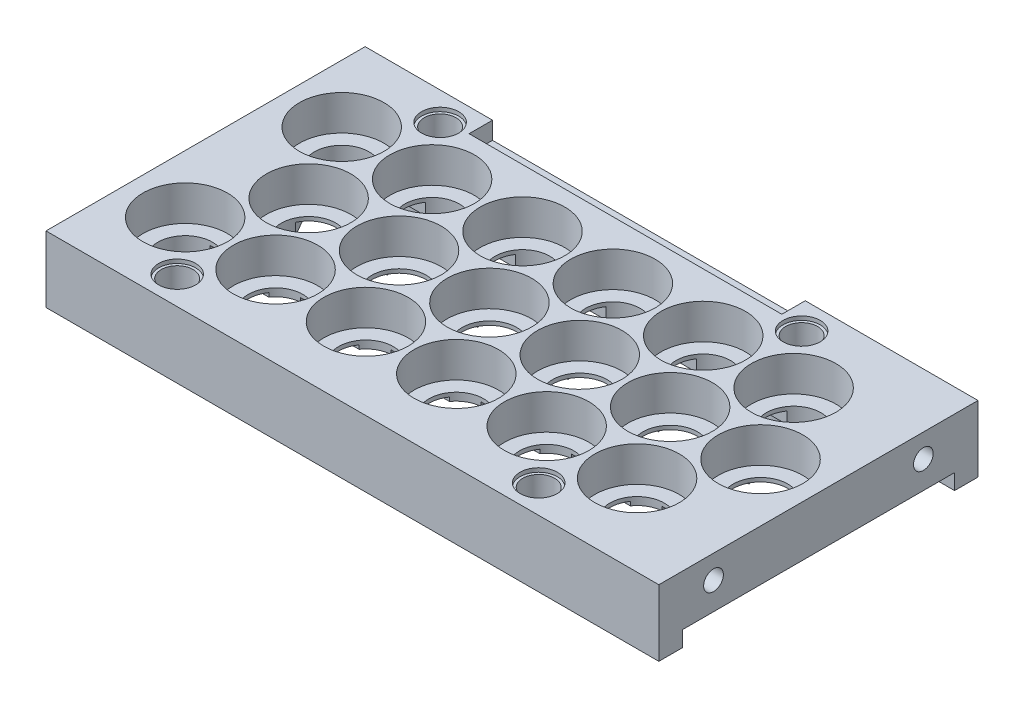
SolidWorks part; units mm, degrees
ref_plane "Front Plane" through (0, 0, 0) normal (0, 0, 1) x (1, 0, 0)
ref_plane "Top Plane" through (0, 0, 0) normal (0, 1, 0) x (1, 0, 0)
ref_plane "Right Plane" through (0, 0, 0) normal (1, 0, 0) x (0, 0, -1)
sketch "Sketch1" plane through (0, 0, 0) normal (0, 1, 0) x (1, 0, 0)
  line L0 (0, 0) -> (11.575, -20.0485) construction
  line L1 (11.575, -20.0485) -> (0, -40.097) construction
  line L2 (0, 0) -> (11.575, 0) construction
  line L3 (11.575, 0) -> (11.575, -20.0485) construction
  line L4 (11.575, -20.0485) -> (11.575, -40.097) construction
  line L5 (11.575, -40.097) -> (0, -40.097) construction
  line L6 (0, 0) -> (23.15, 0) construction
  line L7 (0, 0) -> (23.15, 0) construction
  line L8 (-14.825, -60.922) -> (142.15, -60.922)
  line L9 (-14.825, -60.922) -> (-14.825, 20.825)
  line L10 (-14.825, 20.825) -> (142.15, 20.825)
  line L11 (142.15, -60.922) -> (142.15, 20.825)
  circle A0 centre (0, 0) radius 10.825
  circle A1 centre (11.575, -20.0485) radius 10.825
  circle A2 centre (0, -40.097) radius 10.825
  circle A3 centre (23.15, 0) radius 10.825
  circle A4 centre (34.725, -20.0485) radius 10.825
  circle A5 centre (23.15, -40.097) radius 10.825
  circle A6 centre (46.3, 0) radius 10.825
  circle A7 centre (57.875, -20.0485) radius 10.825
  circle A8 centre (46.3, -40.097) radius 10.825
  circle A9 centre (69.45, 0) radius 10.825
  circle A10 centre (81.025, -20.0485) radius 10.825
  circle A11 centre (69.45, -40.097) radius 10.825
  circle A12 centre (92.6, 0) radius 10.825
  circle A13 centre (104.175, -20.0485) radius 10.825
  circle A14 centre (92.6, -40.097) radius 10.825
  circle A15 centre (115.75, 0) radius 10.825
  circle A16 centre (127.325, -20.0485) radius 10.825
  circle A17 centre (115.75, -40.097) radius 10.825
  circle A18 centre (0, 0) radius 7
  circle A19 centre (11.575, -20.0485) radius 7
  circle A20 centre (0, -40.097) radius 7
  circle A21 centre (23.15, 0) radius 7
  circle A22 centre (34.725, -20.0485) radius 7
  circle A23 centre (23.15, -40.097) radius 7
  circle A24 centre (46.3, 0) radius 7
  circle A25 centre (57.875, -20.0485) radius 7
  circle A26 centre (46.3, -40.097) radius 7
  circle A27 centre (69.45, 0) radius 7
  circle A28 centre (81.025, -20.0485) radius 7
  circle A29 centre (69.45, -40.097) radius 7
  circle A30 centre (92.6, 0) radius 7
  circle A31 centre (104.175, -20.0485) radius 7
  circle A32 centre (92.6, -40.097) radius 7
  circle A33 centre (115.75, 0) radius 7
  circle A34 centre (127.325, -20.0485) radius 7
  circle A35 centre (115.75, -40.097) radius 7
  dimension "D3" = 21.65
  dimension "D11" = 14
  dimension "D1" = 60
  dimension "D2" = 60
  dimension "D4" = 1.5
  dimension "D6" = 23.15
  dimension "D7" = 4
  dimension "D8" = 4
  dimension "D9" = 10
  dimension "D10" = 10
  dimension "D13" = 23.15
  dimension "D5" = 6
  dimension "D12" = 6
extrude "Boss-Extrude2" add sketch "Sketch1" along normal blind 11 contours L8 L11 L10 L9 A17 A16 A15 A14 A13 A12 A11 A10 A9 A8 A7 A6 A5 A4 A3 A2 A1 A0 region at (-13.0551, 0, 20.0485)
extrude "Boss-Extrude3" add sketch "Sketch1<3>" along normal blind 2 contours A0 A18 | A3 A21 | A6 A24 | A9 A27 | A12 A30 | A15 A33 | A1 A19 | A4 A22 | A7 A25 | A10 A28 | A13 A31 | A16 A34 | A17 A35 | A14 A32 | A11 A29 | A8 A26 | A5 A23 | A2 A20 region at (-10.5188, 0, 0) region at (1.0562, 0, 20.0485) region at (-10.5188, 0, 40.097) region at (12.6312, 0, 0) region at (24.2062, 0, 20.0485) region at (12.6312, 0, 40.097) region at (35.7812, 0, 0) region at (47.3562, 0, 20.0485) region at (35.7812, 0, 40.097) region at (58.9312, 0, 0) region at (70.5062, 0, 20.0485) region at (58.9312, 0, 40.097) region at (82.0812, 0, 0) region at (93.6562, 0, 20.0485) region at (82.0812, 0, 40.097) region at (105.2312, 0, 0) region at (116.8062, 0, 20.0485) region at (105.2312, 0, 40.097)
sketch "Sketch1<3>" plane through (0, 0, 0) normal (0, 1, 0) x (1, 0, 0) same geometry as "Sketch1"
sketch "Sketch2" plane through (0, 0, 0) normal (0, -1, 0) x (1, 0, 0)
  line L0 (0, 40.097) -> (11.575, 20.0485) construction
  line L1 (3.4641, 42.097) -> (15.0391, 22.0485)
  line L2 (-3.4641, 38.097) -> (8.1109, 18.0485)
  line L3 (11.575, 20.0485) -> (0, 0) construction
  line L4 (15.0391, 18.0485) -> (3.4641, -2)
  line L5 (8.1109, 22.0485) -> (-3.4641, 2)
  line L6 (19.6859, 38.097) -> (31.2609, 18.0485)
  line L7 (26.6141, 42.097) -> (38.1891, 22.0485)
  line L8 (31.2609, 22.0485) -> (19.6859, 2)
  line L9 (38.1891, 18.0485) -> (26.6141, -2)
  line L10 (23.15, 40.097) -> (34.725, 20.0485) construction
  line L11 (34.725, 20.0485) -> (23.15, 0) construction
  line L12 (42.8359, 38.097) -> (54.4109, 18.0485)
  line L13 (49.7641, 42.097) -> (61.3391, 22.0485)
  line L14 (54.4109, 22.0485) -> (42.8359, 2)
  line L15 (61.3391, 18.0485) -> (49.7641, -2)
  line L16 (46.3, 40.097) -> (57.875, 20.0485) construction
  line L17 (57.875, 20.0485) -> (46.3, 0) construction
  line L18 (65.9859, 38.097) -> (77.5609, 18.0485)
  line L19 (72.9141, 42.097) -> (84.4891, 22.0485)
  line L20 (77.5609, 22.0485) -> (65.9859, 2)
  line L21 (84.4891, 18.0485) -> (72.9141, -2)
  line L22 (69.45, 40.097) -> (81.025, 20.0485) construction
  line L23 (81.025, 20.0485) -> (69.45, 0) construction
  line L24 (89.1359, 38.097) -> (100.7109, 18.0485)
  line L25 (96.0641, 42.097) -> (107.6391, 22.0485)
  line L26 (100.7109, 22.0485) -> (89.1359, 2)
  line L27 (107.6391, 18.0485) -> (96.0641, -2)
  line L28 (92.6, 40.097) -> (104.175, 20.0485) construction
  line L29 (104.175, 20.0485) -> (92.6, 0) construction
  line L30 (112.2859, 38.097) -> (123.8609, 18.0485)
  line L31 (119.2141, 42.097) -> (130.7891, 22.0485)
  line L32 (123.8609, 22.0485) -> (112.2859, 2)
  line L33 (130.7891, 18.0485) -> (119.2141, -2)
  line L34 (115.75, 40.097) -> (127.325, 20.0485) construction
  line L35 (127.325, 20.0485) -> (115.75, 0) construction
  line L36 (-3.4641, 38.097) -> (19.6859, 38.097) construction
  line L37 (0, 40.097) -> (115.75, 40.097) construction
  line L38 (0, 44.097) -> (115.75, 44.097)
  line L39 (0, 36.097) -> (115.75, 36.097)
  line L40 (11.575, 20.0485) -> (127.325, 20.0485) construction
  line L41 (11.575, 24.0485) -> (127.325, 24.0485)
  line L42 (11.575, 16.0485) -> (127.325, 16.0485)
  line L43 (0, 0) -> (115.75, 0) construction
  line L44 (0, 4) -> (115.75, 4)
  line L45 (0, -4) -> (115.75, -4)
  arc A0 (3.4641, 42.097) -> (-3.4641, 38.097) centre (0, 40.097) ccw
  arc A1 (8.1109, 18.0485) -> (15.0391, 22.0485) centre (11.575, 20.0485) ccw
  arc A2 (15.0391, 18.0485) -> (8.1109, 22.0485) centre (11.575, 20.0485) ccw
  arc A3 (-3.4641, 2) -> (3.4641, -2) centre (0, 0) ccw
  arc A4 (26.6141, 42.097) -> (19.6859, 38.097) centre (23.15, 40.097) ccw
  arc A5 (31.2609, 18.0485) -> (38.1891, 22.0485) centre (34.725, 20.0485) ccw
  arc A6 (38.1891, 18.0485) -> (31.2609, 22.0485) centre (34.725, 20.0485) ccw
  arc A7 (19.6859, 2) -> (26.6141, -2) centre (23.15, 0) ccw
  arc A8 (49.7641, 42.097) -> (42.8359, 38.097) centre (46.3, 40.097) ccw
  arc A9 (54.4109, 18.0485) -> (61.3391, 22.0485) centre (57.875, 20.0485) ccw
  arc A10 (61.3391, 18.0485) -> (54.4109, 22.0485) centre (57.875, 20.0485) ccw
  arc A11 (42.8359, 2) -> (49.7641, -2) centre (46.3, 0) ccw
  arc A12 (72.9141, 42.097) -> (65.9859, 38.097) centre (69.45, 40.097) ccw
  arc A13 (77.5609, 18.0485) -> (84.4891, 22.0485) centre (81.025, 20.0485) ccw
  arc A14 (84.4891, 18.0485) -> (77.5609, 22.0485) centre (81.025, 20.0485) ccw
  arc A15 (65.9859, 2) -> (72.9141, -2) centre (69.45, 0) ccw
  arc A16 (96.0641, 42.097) -> (89.1359, 38.097) centre (92.6, 40.097) ccw
  arc A17 (100.7109, 18.0485) -> (107.6391, 22.0485) centre (104.175, 20.0485) ccw
  arc A18 (107.6391, 18.0485) -> (100.7109, 22.0485) centre (104.175, 20.0485) ccw
  arc A19 (89.1359, 2) -> (96.0641, -2) centre (92.6, 0) ccw
  arc A20 (119.2141, 42.097) -> (112.2859, 38.097) centre (115.75, 40.097) ccw
  arc A21 (123.8609, 18.0485) -> (130.7891, 22.0485) centre (127.325, 20.0485) ccw
  arc A22 (130.7891, 18.0485) -> (123.8609, 22.0485) centre (127.325, 20.0485) ccw
  arc A23 (112.2859, 2) -> (119.2141, -2) centre (115.75, 0) ccw
  arc A24 (0, 44.097) -> (0, 36.097) centre (0, 40.097) ccw
  arc A25 (115.75, 36.097) -> (115.75, 44.097) centre (115.75, 40.097) ccw
  arc A26 (11.575, 24.0485) -> (11.575, 16.0485) centre (11.575, 20.0485) ccw
  arc A27 (127.325, 16.0485) -> (127.325, 24.0485) centre (127.325, 20.0485) ccw
  arc A28 (0, 4) -> (0, -4) centre (0, 0) ccw
  arc A29 (115.75, -4) -> (115.75, 4) centre (115.75, 0) ccw
  point P3 (5.7875, 30.0727)
  point P8 (5.7875, 10.0242)
  point P18 (28.9375, 30.0727)
  point P25 (28.9375, 10.0242)
  point P34 (52.0875, 30.0727)
  point P39 (52.0875, 10.0242)
  point P48 (75.2375, 30.0727)
  point P53 (75.2375, 10.0242)
  point P62 (98.3875, 30.0727)
  point P67 (98.3875, 10.0242)
  point P76 (121.5375, 30.0727)
  point P81 (121.5375, 10.0242)
  point P91 (57.875, 40.097)
  point P96 (69.45, 20.0485)
  point P103 (57.875, 0)
  circle M62 centre (0, 0) radius 7
  circle M63 centre (23.15, 0) radius 7
  circle M64 centre (46.3, 0) radius 7
  circle M65 centre (69.45, 0) radius 7
  circle M66 centre (92.6, 0) radius 7
  circle M67 centre (115.75, 0) radius 7
  circle M68 centre (11.575, 20.0485) radius 7
  circle M69 centre (34.725, 20.0485) radius 7
  circle M70 centre (57.875, 20.0485) radius 7
  circle M71 centre (81.025, 20.0485) radius 7
  circle M72 centre (104.175, 20.0485) radius 7
  circle M73 centre (127.325, 20.0485) radius 7
  circle M74 centre (115.75, 40.097) radius 7
  circle M75 centre (92.6, 40.097) radius 7
  circle M76 centre (69.45, 40.097) radius 7
  circle M77 centre (46.3, 40.097) radius 7
  circle M78 centre (23.15, 40.097) radius 7
  circle M79 centre (0, 40.097) radius 7
  dimension "D1" = 8
  dimension "D3" = 23.15
  dimension "D4" = 8
  dimension "D5" = 8
  dimension "D6" = 8
extrude "Cut-Extrude1" cut sketch "Sketch2" against normal blind 1 contours L1 L39 L38 M78 M79 | L7 L39 L38 M77 M78 | L39 L2 L1 M79 M68 | L42 L8 L6 L41 M68 M69 | L6 L41 L7 L39 M69 M78 | L12 L41 L13 L39 M70 M77 | L13 L39 L38 M76 M77 | L18 L41 L19 L39 M71 M76 | L19 L39 L38 M75 M76 | L24 L41 L25 L39 M72 M75 | L25 L39 L38 M74 M75 | L30 L41 L31 M73 M74 | L42 L32 L30 L41 M72 M73 | L42 L26 L24 L41 M71 M72 | L42 L20 L18 L41 M70 M71 | L42 L14 L12 L41 M69 M70 | L45 L44 L4 M62 M63 | L44 L4 L5 M62 M68 | L45 L44 L9 M63 M64 | L45 L44 L15 M64 M65 | L45 L44 L21 M65 M66 | L45 L44 L27 M66 M67 | L44 L27 L42 L26 M66 M72 | L42 L32 L33 M67 M73 | L44 L21 L42 L20 M65 M71 | L44 L15 L42 L14 M64 M70 | L39 L13 M77 | L39 L25 M75 | L39 L19 M76 | L41 L6 M69 | L44 L4 M62 | L44 L15 M64 | L44 L21 M65 | L44 L27 M66 | L41 L30 M73 | L32 L42 M73 | L41 L24 M72 | L26 L42 M72 | L41 L18 M71 | L20 L42 M71 | L41 L12 M70 | L14 L42 M70 | L44 L9 L42 L8 M63 M69 | L8 L42 M69 | L39 L7 M78 | L39 L1 M79 | L44 A29 L45 A28 region at (11.6138, 0, 40.1242) region at (6.3461, 0, 36.4331) region at (5.7834, 0, 30.0255) region at (23.0718, 0, 20.0485) region at (28.9375, 0, 30.0727) region at (34.7638, 0, 40.1242) region at (28.3789, 0, 23.7124) region at (5.7834, 0, 10.0715) region at (29.4961, 0, 36.4331) region at (57.9138, 0, 40.1242) region at (28.3789, 0, 16.3846) region at (28.9375, 0, 10.0242) region at (6.3461, 0, 3.6639) region at (11.6138, 0, -0.0272) region at (52.0875, 0, 30.0727) region at (46.2218, 0, 20.0485) region at (52.6461, 0, 36.4331) region at (81.0638, 0, 40.1242) region at (51.5289, 0, 23.7124) region at (34.7638, 0, -0.0272) region at (75.2375, 0, 30.0727) region at (75.7961, 0, 36.4331) region at (104.2138, 0, 40.1242) region at (74.6789, 0, 23.7124) region at (69.3718, 0, 20.0485) region at (51.5289, 0, 16.3846) region at (52.0875, 0, 10.0242) region at (57.9138, 0, -0.0272) region at (98.3875, 0, 30.0727) region at (98.9461, 0, 36.4331) region at (97.8289, 0, 23.7124) region at (92.5218, 0, 20.0485) region at (74.6789, 0, 16.3846) region at (52.6461, 0, 3.6639) region at (81.0638, 0, -0.0272) region at (121.5416, 0, 30.12) region at (75.2375, 0, 10.0242) region at (120.9789, 0, 23.7124) region at (115.6718, 0, 20.0485) region at (97.8289, 0, 16.3846) region at (75.7961, 0, 3.6639) region at (104.2138, 0, -0.0272) region at (98.3875, 0, 10.0242) region at (121.5416, 0, 9.977) region at (120.9789, 0, 16.3846) region at (98.9461, 0, 3.6639)
sketch "Sketch9" plane through (0, 11, 0) normal (0, 1, 0) x (1, 0, 0)
  line L0 (11.575, -60.922) -> (11.575, 20.825)
  line L1 (-14.825, 20.825) -> (142.15, 20.825) construction
  line L2 (104.175, 20.825) -> (104.175, -60.922)
  line L3 (-14.825, -60.922) -> (142.15, -60.922) construction
  circle A0 centre (11.575, 13.625) radius 4.0767
  circle A1 centre (11.575, -53.722) radius 4.0767
  circle A2 centre (104.175, -53.722) radius 4.0767
  circle A3 centre (104.175, 13.625) radius 4.0767
  point P0 (11.575, 13.625)
  point P7 (11.575, -20.0485)
  point P15 (104.175, -20.0485)
  point P20 (104.175, 13.625)
  point P21 (104.175, -53.722)
  point P22 (11.575, -53.722)
  dimension "D5" = 8.1534
  dimension "D1" = 7.2
  dimension "D4" = 7.2
extrude "Cut-Extrude3" cut sketch "Sketch9" against normal up to next contours A2 | A1 | A0 | A3
sketch "Sketch10" plane through (0, 11, 0) normal (0, 1, 0) x (1, 0, 0)
  circle A0 centre (11.575, 13.625) radius 4.7625
  circle A1 centre (104.175, 13.625) radius 4.7625
  circle A2 centre (104.175, -53.722) radius 4.7625
  circle A3 centre (11.575, -53.722) radius 4.7625
  dimension "D1" = 9.525
extrude "Cut-Extrude4" cut sketch "Sketch10" against normal blind 1
sketch "Sketch13" plane through (0, 0, 0) normal (0, -1, 0) x (1, 0, 0)
  line L0 (142.15, 60.922) -> (142.15, -20.825) construction
  line L5 (3.575, 53.722) -> (3.575, 60.922)
  line L8 (-14.825, 60.922) -> (142.15, 60.922) construction
  line L9 (3.575, 60.922) -> (19.575, 60.922)
  line L10 (19.575, 60.922) -> (19.575, 53.722)
  line L12 (57.875, 20.0485) -> (57.875, -20.825) construction
  line L13 (-14.825, -20.825) -> (142.15, -20.825) construction
  line L14 (11.575, 20.0485) -> (127.325, 20.0485) construction
  line L16 (96.175, 60.922) -> (96.175, 53.722)
  line L17 (112.175, 60.922) -> (96.175, 60.922)
  line L18 (112.175, 53.722) -> (112.175, 60.922)
  line L19 (-14.825, 60.922) -> (142.15, 60.922)
  line L20 (-14.825, 60.922) -> (-14.825, 54.922)
  line L21 (-14.825, 54.922) -> (142.15, 54.922)
  line L22 (142.15, 60.922) -> (142.15, 54.922)
  line L23 (142.15, -20.825) -> (142.15, -14.825)
  line L24 (-14.825, -14.825) -> (142.15, -14.825)
  line L25 (-14.825, -20.825) -> (-14.825, -14.825)
  line L26 (-14.825, -20.825) -> (142.15, -20.825)
  line L27 (112.175, -13.625) -> (112.175, -20.825)
  line L28 (112.175, -20.825) -> (96.175, -20.825)
  line L29 (96.175, -20.825) -> (96.175, -13.625)
  line L32 (19.575, -20.825) -> (19.575, -13.625)
  line L33 (3.575, -20.825) -> (19.575, -20.825)
  line L34 (3.575, -13.625) -> (3.575, -20.825)
  circle A4 centre (11.575, 53.722) radius 6.5
  circle A5 centre (11.575, 53.722) radius 8
  circle A6 centre (104.175, 53.722) radius 8
  circle A7 centre (104.175, 53.722) radius 6.5
  circle A8 centre (104.175, -13.625) radius 6.5
  circle A9 centre (104.175, -13.625) radius 8
  circle A10 centre (11.575, -13.625) radius 8
  circle A11 centre (11.575, -13.625) radius 6.5
  line M15 (142.15, 60.922) -> (-14.825, 60.922)
  line M16 (-14.825, 60.922) -> (-14.825, -20.825)
  line M17 (-14.825, -20.825) -> (142.15, -20.825)
  line M18 (142.15, -20.825) -> (142.15, 60.922)
  dimension "D1" = 13
  dimension "D2" = 16
  dimension "D3" = 6
extrude "Boss-Extrude7" add sketch "Sketch13" along normal blind 6 contours L21 L5 M16 M15 | A5 L5 L21 M15 | A5 L21 L10 M15 | L10 L21 L16 M15 | L21 A5 L19 A4 | A5 L21 A4 | L21 A6 L16 M15 | L21 A7 A6 L19 | L21 A7 A6 | A6 L21 L18 M15 | L18 L21 M18 M15 | A9 L24 L29 L26 | L28 A9 L24 A8 | A9 L26 L27 L24 | L24 L27 L26 M18 | L32 L26 L29 L24 | L24 A9 A8 | L34 L24 M16 M17 | L26 A10 L24 L34 | L24 A11 A10 | L24 A11 A10 L33 | L24 A10 L26 L32 region at (3.7817, 0, 54.3098) region at (-5.625, 0, 57.922) region at (4.8282, 0, 59.2567) region at (5.2714, 0, 58.3681) region at (18.3218, 0, 59.2567) region at (57.875, 0, 57.922) region at (-5.625, 0, -17.825) region at (97.4282, 0, 59.2567) region at (4.8282, 0, -19.1597) region at (96.3817, 0, 54.3098) region at (97.8714, 0, 58.3681) region at (3.7817, 0, -14.2128) region at (4.4261, 0, -14.9942) region at (110.9218, 0, 59.2567) region at (127.1625, 0, 57.922) region at (18.3218, 0, -19.1597) region at (57.875, 0, -17.825) region at (97.4282, 0, -19.1597) region at (127.1625, 0, -17.825) region at (96.3817, 0, -14.2128) region at (97.0261, 0, -14.9942) region at (110.9218, 0, -19.1597)
sketch "Sketch14" plane through (0, 0, 0) normal (0, -1, 0) x (1, 0, 0)
  line L2 (142.15, 54.922) -> (142.15, -14.825) construction
  line L4 (5.2386, 17.0736) -> (-0.5918, 6.9749) construction
  line L5 (5.7446, -4) -> (17.4054, -4) construction
  line L6 (28.8946, -4) -> (40.5554, -4) construction
  line L7 (52.0446, -4) -> (63.7054, -4) construction
  line L8 (75.1946, -4) -> (86.8554, -4) construction
  line L9 (98.3446, -4) -> (110.0054, -4) construction
  line L10 (127.9168, 13.0736) -> (122.0864, 2.9749) construction
  line L11 (122.0864, 37.122) -> (127.9168, 27.0234) construction
  line L12 (98.3446, 44.097) -> (110.0054, 44.097) construction
  line L13 (75.1946, 44.097) -> (86.8554, 44.097) construction
  line L14 (52.0446, 44.097) -> (63.7054, 44.097) construction
  line L15 (28.8946, 44.097) -> (40.5554, 44.097) construction
  line L16 (-0.5918, 33.122) -> (5.2386, 23.0234) construction
  line L17 (5.7446, 44.097) -> (17.4054, 44.097) construction
  line L20 (142.15, 54.922) -> (142.15, -14.825)
  line L22 (5.2386, 17.0736) -> (-0.5918, 6.9749)
  line L23 (5.7446, -4) -> (17.4054, -4)
  line L24 (28.8946, -4) -> (40.5554, -4)
  line L25 (52.0446, -4) -> (63.7054, -4)
  line L26 (75.1946, -4) -> (86.8554, -4)
  line L27 (98.3446, -4) -> (110.0054, -4)
  line L28 (127.9168, 13.0736) -> (122.0864, 2.9749)
  line L29 (122.0864, 37.122) -> (127.9168, 27.0234)
  line L30 (98.3446, 44.097) -> (110.0054, 44.097)
  line L31 (75.1946, 44.097) -> (86.8554, 44.097)
  line L32 (52.0446, 44.097) -> (63.7054, 44.097)
  line L33 (28.8946, 44.097) -> (40.5554, 44.097)
  line L34 (-0.5918, 33.122) -> (5.2386, 23.0234)
  line L35 (5.7446, 44.097) -> (17.4054, 44.097)
  line L36 (112.0845, -14.825) -> (142.15, -14.825) construction
  line L37 (19.4845, -14.825) -> (96.2655, -14.825) construction
  line L38 (-14.825, -14.825) -> (3.6655, -14.825) construction
  line L39 (-14.825, 54.922) -> (-14.825, -14.825) construction
  line L40 (112.0845, 54.922) -> (142.15, 54.922) construction
  line L41 (19.4845, 54.922) -> (96.2655, 54.922) construction
  line L42 (-14.825, 54.922) -> (3.6655, 54.922) construction
  line L43 (112.0845, -14.825) -> (142.15, -14.825)
  line L44 (19.4845, -14.825) -> (96.2655, -14.825)
  line L45 (-14.825, -14.825) -> (3.6655, -14.825)
  line L46 (-14.825, 54.922) -> (-14.825, -14.825)
  line L47 (112.0845, 54.922) -> (142.15, 54.922)
  line L48 (19.4845, 54.922) -> (96.2655, 54.922)
  line L49 (-14.825, 54.922) -> (3.6655, 54.922)
  arc A3 (5.2386, 23.0234) -> (5.2386, 17.0736) centre (11.575, 20.0485) ccw construction
  arc A4 (-0.5918, 6.9749) -> (5.7446, -4) centre (0, 0) ccw construction
  arc A5 (17.4054, -4) -> (28.8946, -4) centre (23.15, 0) ccw construction
  arc A6 (40.5554, -4) -> (52.0446, -4) centre (46.3, 0) ccw construction
  arc A7 (63.7054, -4) -> (75.1946, -4) centre (69.45, 0) ccw construction
  arc A8 (86.8554, -4) -> (98.3446, -4) centre (92.6, 0) ccw construction
  arc A9 (110.0054, -4) -> (122.0864, 2.9749) centre (115.75, 0) ccw construction
  arc A10 (127.9168, 13.0736) -> (127.9168, 27.0234) centre (127.325, 20.0485) ccw construction
  arc A11 (122.0864, 37.122) -> (110.0054, 44.097) centre (115.75, 40.097) ccw construction
  arc A12 (98.3446, 44.097) -> (86.8554, 44.097) centre (92.6, 40.097) ccw construction
  arc A13 (75.1946, 44.097) -> (63.7054, 44.097) centre (69.45, 40.097) ccw construction
  arc A14 (52.0446, 44.097) -> (40.5554, 44.097) centre (46.3, 40.097) ccw construction
  arc A16 (28.8946, 44.097) -> (17.4054, 44.097) centre (23.15, 40.097) ccw construction
  arc A17 (5.7446, 44.097) -> (-0.5918, 33.122) centre (0, 40.097) ccw construction
  arc A21 (5.2386, 23.0234) -> (5.2386, 17.0736) centre (11.575, 20.0485) ccw
  arc A22 (-0.5918, 6.9749) -> (5.7446, -4) centre (0, 0) ccw
  arc A23 (17.4054, -4) -> (28.8946, -4) centre (23.15, 0) ccw
  arc A24 (40.5554, -4) -> (52.0446, -4) centre (46.3, 0) ccw
  arc A25 (63.7054, -4) -> (75.1946, -4) centre (69.45, 0) ccw
  arc A26 (86.8554, -4) -> (98.3446, -4) centre (92.6, 0) ccw
  arc A27 (110.0054, -4) -> (122.0864, 2.9749) centre (115.75, 0) ccw
  arc A28 (127.9168, 13.0736) -> (127.9168, 27.0234) centre (127.325, 20.0485) ccw
  arc A29 (122.0864, 37.122) -> (110.0054, 44.097) centre (115.75, 40.097) ccw
  arc A30 (98.3446, 44.097) -> (86.8554, 44.097) centre (92.6, 40.097) ccw
  arc A31 (75.1946, 44.097) -> (63.7054, 44.097) centre (69.45, 40.097) ccw
  arc A32 (52.0446, 44.097) -> (40.5554, 44.097) centre (46.3, 40.097) ccw
  arc A34 (28.8946, 44.097) -> (17.4054, 44.097) centre (23.15, 40.097) ccw
  arc A35 (5.7446, 44.097) -> (-0.5918, 33.122) centre (0, 40.097) ccw
  arc A36 (112.0845, -14.825) -> (96.2655, -14.825) centre (104.175, -13.625) ccw construction
  arc A37 (19.4845, -14.825) -> (3.6655, -14.825) centre (11.575, -13.625) ccw construction
  arc A38 (96.2655, 54.922) -> (112.0845, 54.922) centre (104.175, 53.722) ccw construction
  arc A39 (3.6655, 54.922) -> (19.4845, 54.922) centre (11.575, 53.722) ccw construction
  arc A40 (112.0845, -14.825) -> (96.2655, -14.825) centre (104.175, -13.625) ccw
  arc A41 (19.4845, -14.825) -> (3.6655, -14.825) centre (11.575, -13.625) ccw
  arc A42 (96.2655, 54.922) -> (112.0845, 54.922) centre (104.175, 53.722) ccw
  arc A43 (3.6655, 54.922) -> (19.4845, 54.922) centre (11.575, 53.722) ccw
extrude "Boss-Extrude9" add sketch "Sketch14" along normal blind 2
sketch "Sketch16" plane through (0, 0, 0) normal (0, -1, 0) x (1, 0, 0)
  line L0 (17.4054, 36.097) -> (12.1668, 27.0234) construction
  line L1 (12.1668, 27.0234) -> (17.3196, 24.0485) construction
  line L2 (17.3196, 24.0485) -> (22.5582, 33.122) construction
  line L3 (22.5582, 33.122) -> (17.4054, 36.097) construction
  line L4 (14.7861, 31.5602) -> (19.9389, 28.5853) construction
  line L5 (15.5361, 32.8592) -> (20.6889, 29.8843)
  line L6 (14.0361, 30.2612) -> (19.1889, 27.2862)
  line L7 (11.575, 20.0485) -> (126.446, 20.0485) construction
  line L8 (40.5554, 36.097) -> (35.3168, 27.0234) construction
  line L9 (35.3168, 27.0234) -> (40.4696, 24.0485) construction
  line L10 (40.4696, 24.0485) -> (45.7082, 33.122) construction
  line L11 (45.7082, 33.122) -> (40.5554, 36.097) construction
  line L12 (37.9361, 31.5602) -> (43.0889, 28.5853) construction
  line L13 (38.6861, 32.8592) -> (43.8389, 29.8843)
  line L14 (37.1861, 30.2612) -> (42.3389, 27.2862)
  line L15 (63.7054, 36.097) -> (58.4668, 27.0234) construction
  line L16 (58.4668, 27.0234) -> (63.6196, 24.0485) construction
  line L17 (63.6196, 24.0485) -> (68.8582, 33.122) construction
  line L18 (68.8582, 33.122) -> (63.7054, 36.097) construction
  line L19 (61.0861, 31.5602) -> (66.2389, 28.5853) construction
  line L20 (61.8361, 32.8592) -> (66.9889, 29.8843)
  line L21 (60.3361, 30.2612) -> (65.4889, 27.2862)
  line L22 (86.8554, 36.097) -> (81.6168, 27.0234) construction
  line L23 (81.6168, 27.0234) -> (86.7696, 24.0485) construction
  line L24 (86.7696, 24.0485) -> (92.0082, 33.122) construction
  line L25 (92.0082, 33.122) -> (86.8554, 36.097) construction
  line L26 (84.2361, 31.5602) -> (89.3889, 28.5853) construction
  line L27 (84.9861, 32.8592) -> (90.1389, 29.8843)
  line L28 (83.4861, 30.2612) -> (88.6389, 27.2862)
  line L29 (110.0054, 36.097) -> (104.7668, 27.0234) construction
  line L30 (104.7668, 27.0234) -> (109.9196, 24.0485) construction
  line L31 (109.9196, 24.0485) -> (115.1582, 33.122) construction
  line L32 (115.1582, 33.122) -> (110.0054, 36.097) construction
  line L33 (107.3861, 31.5602) -> (112.5389, 28.5853) construction
  line L34 (108.1361, 32.8592) -> (113.2889, 29.8843)
  line L35 (106.6361, 30.2612) -> (111.7889, 27.2862)
  line L36 (14.7861, 8.5368) -> (19.9389, 11.5117) construction
  line L37 (15.5361, 7.2377) -> (20.6889, 10.2127)
  line L38 (14.0361, 9.8358) -> (19.1889, 12.8108)
  line L39 (37.9361, 8.5368) -> (43.0889, 11.5117) construction
  line L40 (38.6861, 7.2377) -> (43.8389, 10.2127)
  line L41 (37.1861, 9.8358) -> (42.3389, 12.8108)
  line L42 (61.0861, 8.5368) -> (66.2389, 11.5117) construction
  line L43 (61.8361, 7.2377) -> (66.9889, 10.2127)
  line L44 (60.3361, 9.8358) -> (65.4889, 12.8108)
  line L45 (84.2361, 8.5368) -> (89.3889, 11.5117) construction
  line L46 (84.9861, 7.2377) -> (90.1389, 10.2127)
  line L47 (83.4861, 9.8358) -> (88.6389, 12.8108)
  line L48 (107.3861, 8.5368) -> (112.5389, 11.5117) construction
  line L49 (108.1361, 7.2377) -> (113.2889, 10.2127)
  line L50 (106.6361, 9.8358) -> (111.7889, 12.8108)
  line L51 (115.1582, 6.9749) -> (110.0054, 4) construction
  line L52 (109.9196, 16.0485) -> (115.1582, 6.9749) construction
  line L53 (104.7668, 13.0736) -> (109.9196, 16.0485) construction
  line L54 (110.0054, 4) -> (104.7668, 13.0736) construction
  line L55 (92.0082, 6.9749) -> (86.8554, 4) construction
  line L56 (86.7696, 16.0485) -> (92.0082, 6.9749) construction
  line L57 (81.6168, 13.0736) -> (86.7696, 16.0485) construction
  line L58 (86.8554, 4) -> (81.6168, 13.0736) construction
  line L59 (68.8582, 6.9749) -> (63.7054, 4) construction
  line L60 (63.6196, 16.0485) -> (68.8582, 6.9749) construction
  line L61 (58.4668, 13.0736) -> (63.6196, 16.0485) construction
  line L62 (63.7054, 4) -> (58.4668, 13.0736) construction
  line L63 (45.7082, 6.9749) -> (40.5554, 4) construction
  line L64 (40.4696, 16.0485) -> (45.7082, 6.9749) construction
  line L65 (35.3168, 13.0736) -> (40.4696, 16.0485) construction
  line L66 (40.5554, 4) -> (35.3168, 13.0736) construction
  line L67 (22.5582, 6.9749) -> (17.4054, 4) construction
  line L68 (17.3196, 16.0485) -> (22.5582, 6.9749) construction
  line L69 (12.1668, 13.0736) -> (17.3196, 16.0485) construction
  line L70 (17.4054, 4) -> (12.1668, 13.0736) construction
  arc A0 (15.5361, 32.8592) -> (14.0361, 30.2612) centre (14.7861, 31.5602) ccw
  arc A1 (19.1889, 27.2862) -> (20.6889, 29.8843) centre (19.9389, 28.5853) ccw
  arc A2 (38.6861, 32.8592) -> (37.1861, 30.2612) centre (37.9361, 31.5602) ccw
  arc A3 (42.3389, 27.2862) -> (43.8389, 29.8843) centre (43.0889, 28.5853) ccw
  arc A4 (61.8361, 32.8592) -> (60.3361, 30.2612) centre (61.0861, 31.5602) ccw
  arc A5 (65.4889, 27.2862) -> (66.9889, 29.8843) centre (66.2389, 28.5853) ccw
  arc A6 (84.9861, 32.8592) -> (83.4861, 30.2612) centre (84.2361, 31.5602) ccw
  arc A7 (88.6389, 27.2862) -> (90.1389, 29.8843) centre (89.3889, 28.5853) ccw
  arc A8 (108.1361, 32.8592) -> (106.6361, 30.2612) centre (107.3861, 31.5602) ccw
  arc A9 (111.7889, 27.2862) -> (113.2889, 29.8843) centre (112.5389, 28.5853) ccw
  arc A10 (40.5554, 36.097) -> (45.7082, 33.122) centre (46.3, 40.097) ccw construction
  arc A11 (15.5361, 7.2377) -> (14.0361, 9.8358) centre (14.7861, 8.5368) cw
  arc A12 (19.1889, 12.8108) -> (20.6889, 10.2127) centre (19.9389, 11.5117) cw
  arc A13 (38.6861, 7.2377) -> (37.1861, 9.8358) centre (37.9361, 8.5368) cw
  arc A14 (42.3389, 12.8108) -> (43.8389, 10.2127) centre (43.0889, 11.5117) cw
  arc A15 (61.8361, 7.2377) -> (60.3361, 9.8358) centre (61.0861, 8.5368) cw
  arc A16 (65.4889, 12.8108) -> (66.9889, 10.2127) centre (66.2389, 11.5117) cw
  arc A17 (84.9861, 7.2377) -> (83.4861, 9.8358) centre (84.2361, 8.5368) cw
  arc A18 (88.6389, 12.8108) -> (90.1389, 10.2127) centre (89.3889, 11.5117) cw
  arc A19 (108.1361, 7.2377) -> (106.6361, 9.8358) centre (107.3861, 8.5368) cw
  arc A20 (111.7889, 12.8108) -> (113.2889, 10.2127) centre (112.5389, 11.5117) cw
  point P10 (17.3625, 30.0727)
  point P25 (40.5125, 30.0727)
  point P36 (63.6625, 30.0727)
  point P47 (86.8125, 30.0727)
  point P58 (109.9625, 30.0727)
  point P68 (17.3625, 10.0242)
  point P75 (40.5125, 10.0242)
  point P82 (63.6625, 10.0242)
  point P89 (86.8125, 10.0242)
  point P96 (109.9625, 10.0242)
  dimension "D1" = 1.5
  dimension "D2" = 5
extrude "Boss-Extrude10" add sketch "Sketch16" along normal blind 2
sketch "Sketch17" plane through (0, -2, 0) normal (0, -1, 0) x (-1, 0, 0)
  line L0 (-57.875, -44.097) -> (-57.875, -54.922) construction
  line L1 (-63.7054, -44.097) -> (-52.0446, -44.097) construction
  line L2 (-19.4845, -54.922) -> (-96.2655, -54.922) construction
  line L3 (-142.15, 14.825) -> (-142.15, -54.922) construction
  line L4 (14.825, -54.922) -> (14.825, 14.825) construction
  line L5 (10.825, -49.5095) -> (-57.875, -49.5095) construction
  line L6 (-57.875, -49.5095) -> (-132.15, -49.5095) construction
  line L7 (-127.325, -20.0485) -> (-11.575, -20.0485)
  line L8 (-57.875, 9.4125) -> (-132.15, 9.4125) construction
  line L9 (10.825, 9.4125) -> (-57.875, 9.4125) construction
  line L10 (-57.875, 4) -> (-57.875, 14.825) construction
  circle A0 centre (10.825, -49.5095) radius 1.9431
  circle A1 centre (-57.875, -49.5095) radius 1.9431
  circle A2 centre (-132.15, -49.5095) radius 1.9431
  circle A3 centre (-132.15, 9.4125) radius 1.9431
  circle A4 centre (-57.875, 9.4125) radius 1.9431
  circle A5 centre (10.825, 9.4125) radius 1.9431
  dimension "D1" = 3.8862
  dimension "D2" = 10
  dimension "D3" = 4
extrude "Cut-Extrude5" cut sketch "Sketch17" against normal blind 3.81 contours A3 | A2 | A4 | A5 | A0 | A1 region at (-10.825, -2, 49.5095) region at (57.875, -2, 49.5095) region at (132.15, -2, 49.5095) region at (132.15, -2, -9.4125) region at (57.875, -2, -9.4125) region at (-10.825, -2, -9.4125)
sketch "Sketch18" plane through (0, 0, -20.825) normal (0, 0, -1) x (-1, 0, 0)
  line L1 (-97.9, 11) -> (-17.8, 11)
  line L2 (-97.9, 11) -> (-17.8, 11)
  line L3 (-97.9, 11) -> (-97.9, 6.525)
  line L4 (-17.8, 11) -> (-17.8, 6.525)
  line L5 (-97.9, 6.525) -> (-17.8, 6.525)
  line L6 (-104.15, 11) -> (-11.55, 11)
  line L7 (14.825, 11) -> (-142.15, 11) construction
  point P7 (-57.85, 11)
  point P10 (-57.85, 11)
  line M8 (14.825, 11) -> (-142.15, 11)
  dimension "D1" = 80.1
  dimension "D2" = 4.475
  dimension "D3" = 92.6
  dimension "D4" = 38
extrude "Cut-Extrude6" cut sketch "Sketch18" against normal blind 6 contours L3 L5 L4 M8 region at (57.85, 8.7625, -20.825)
sketch "Sketch19" plane through (0, 0, -20.825) normal (0, 0, -1) x (-1, 0, 0)
  line L0 (-85.9, 6.525) -> (-29.8, 6.525)
  line L1 (-85.9, 6.525) -> (-85.9, 0.2625)
  line L2 (-29.8, 6.525) -> (-29.8, 0.2625)
  line L3 (-85.9, 0.2625) -> (-29.8, 0.2625)
  line L4 (-97.9, 6.525) -> (-17.8, 6.525) construction
  line L5 (-97.9, 6.525) -> (-17.8, 6.525) construction
  line L6 (-85.9, 6.525) -> (-97.9, 6.525) construction
  line L7 (-29.8, 6.525) -> (-17.8, 6.525) construction
  line L8 (-57.85, 6.525) -> (-57.85, -6)
  line L9 (14.825, -6) -> (-142.15, -6) construction
  circle A0 centre (-85.9, 0.2625) radius 1.9431
  circle A1 centre (-29.8, 0.2625) radius 1.9431
  point P17 (-57.85, 0.2625)
  dimension "D2" = 3.8862
  dimension "D1" = 12
extrude "Cut-Extrude7" cut sketch "Sketch19" against normal blind 5 contours L1 A0 L3 | L3 A0 L1 | L3 A1 L2 | L2 A1 L3 region at (85.0753, 1.0872, -20.825) region at (86.1749, -0.0124, -20.825) region at (29.5251, -0.0124, -20.825) region at (30.6247, 1.0872, -20.825)
sketch "Sketch20" plane through (142.15, 0, 0) normal (1, 0, 0) x (0, 0, -1)
  line L0 (-46.922, 5) -> (-60.922, 5)
  line L1 (6.825, 5) -> (20.825, 5)
  line L2 (-46.922, 5) -> (-46.922, 11)
  line L3 (6.825, 5) -> (6.825, 11)
  line L4 (-60.922, 11) -> (20.825, 11) construction
  line L5 (20.825, 11) -> (20.825, -6) construction
  line L6 (-60.922, 11) -> (-60.922, -6) construction
  circle A0 centre (-46.922, 5) radius 2.5273
  circle A1 centre (6.825, 5) radius 2.5273
  dimension "D1" = 5.0546
  dimension "D2" = 14
  dimension "D3" = 6
extrude "Cut-Extrude8" cut sketch "Sketch20" against normal blind 10 contours L0 A0 L2 | L2 A0 L0 | A1 region at (142.15, 4.6425, 46.5644) region at (142.15, 6.0726, 47.9946)
equation "\"hole_diameter\"= 21.65"
equation "\"D3@Sketch1\"=\"hole_diameter\""
equation "\"cell_spacing\"= 1.5"
equation "\"D4@Sketch1\"=\"cell_spacing\""
equation "\"D6@Sketch1\"=\"hole_diameter\"+\"cell_spacing\""
equation "\"len_spacing\"= 4"
equation "\"D7@Sketch1\"=\"len_spacing\""
equation "\"D8@Sketch1\"=\"len_spacing\""
equation "\"wid_spacing\"= 10"
equation "\"D9@Sketch1\"=\"wid_spacing\""
equation "\"D10@Sketch1\"=\"wid_spacing\""
equation "\"nipple\"= 14"
equation "\"D11@Sketch1\"=\"nipple\""
equation "\"D13@Sketch1\"=\"hole_diameter\"+\"cell_spacing\""
equation "\"channel\"= 8"
equation "\"D1@Sketch2\"=\"channel\""
equation "\"D3@Sketch2\"=\"hole_diameter\"+\"cell_spacing\""
equation "\"D4@Sketch2\"=\"channel\""
equation "\"D5@Sketch2\"=\"channel\""
equation "\"D6@Sketch2\"=\"channel\""
equation "\"lip\"= 6"
equation "\"lip_height\"= 1"
equation "\"outer_fillet\"=6"
equation "\"insert_placement\"= 7.2"
equation "\"D4@Sketch9\"=\"insert_placement\""
equation "\"D1@Sketch9\"=\"insert_placement\""
equation "\"heat_insert_diameter\"=8.1534"
equation "\"D5@Sketch9\"=\"heat_insert_diameter\""
equation "\"heat_insert_lip_diameter\"=9.525"
equation "\"D1@Sketch10\"=\"heat_insert_lip_diameter\""
equation "\"bolt_head_diameter\"=13"
equation "\"D1@Sketch13\"=\"bolt_head_diameter\""
equation "\"D2@Sketch13\"=\"bolt_head_diameter\"+3"
equation "\"D3@Sketch13\"=\"lip\""
equation "\"small_heat_insert\" = .153in"
equation "\"D1@Sketch17\"=\"small_heat_insert\""
equation "\"bdm_cut_depth\"=6"
equation "\"D1@Cut-Extrude6\"=\"bdm_cut_depth\""
equation "\"D2@Sketch19\"=\"small_heat_insert\""
equation "\"heat_insert_depth\"=3.81"
equation "\"D1@Cut-Extrude5\"=\"heat_insert_depth\""
equation "\"heat_insert_space\"=6"
equation "\"heat_insert\"=5.5"
